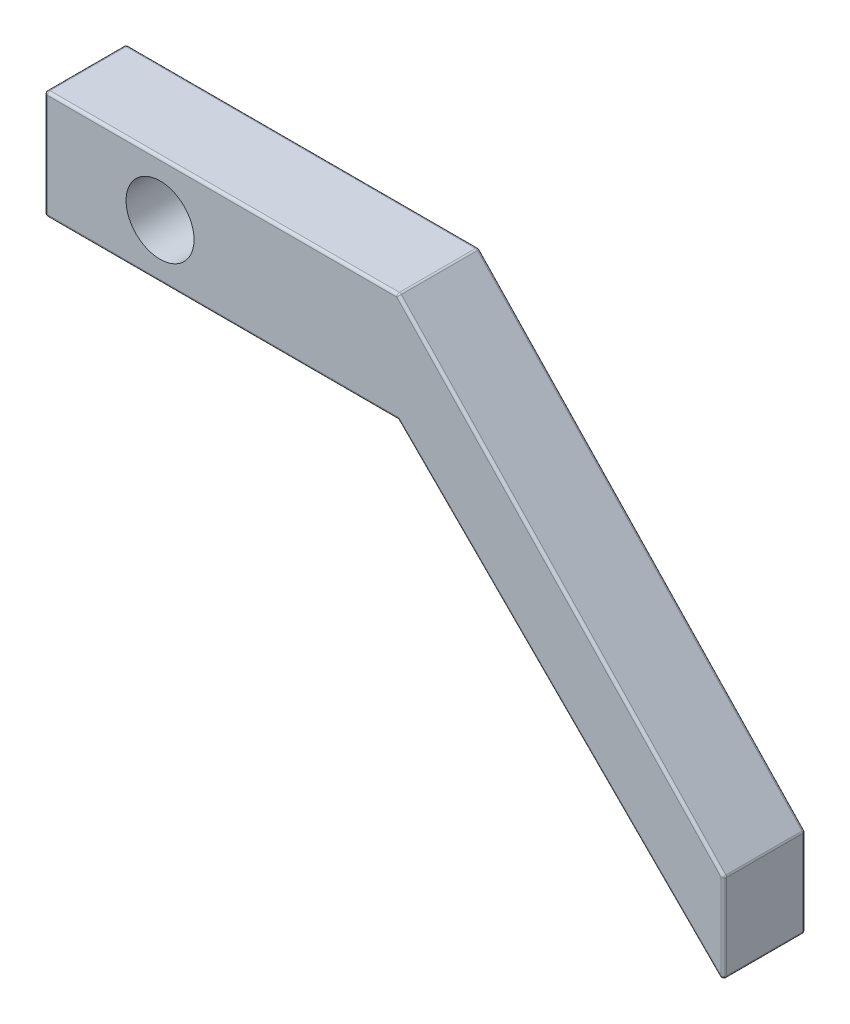
SolidWorks part; units mm, degrees
ref_plane "前视基准面" through (0, 0, 0) normal (0, 0, 1) x (1, 0, 0)
ref_plane "上视基准面" through (0, 0, 0) normal (0, 1, 0) x (1, 0, 0)
ref_plane "右视基准面" through (0, 0, 0) normal (1, 0, 0) x (0, 0, -1)
sketch "草图1" plane through (0, 0, 0) normal (0, 0, 1) x (1, 0, 0)
  line L0 (80, -20) -> (179.4574, -119.4574)
  line L1 (-80, 20) -> (80, 20)
  line L2 (-80, 20) -> (-80, -20)
  line L3 (-80, -20) -> (80, -20)
  line L4 (80, 20) -> (80, -20)
  line L5 (-80, 20) -> (80, -20) construction
  line L6 (-80, -20) -> (80, 20) construction
  line L7 (40, 20) -> (80, 20)
  line L8 (40, 20) -> (40, -20)
  line L9 (40, -20) -> (80, -20)
  line L10 (80, 20) -> (80, -20)
  line L11 (40, 20) -> (80, -20) construction
  line L12 (40, -20) -> (80, 20) construction
  line L13 (80, 20) -> (200, -105.8673)
  line L14 (200, -105.8673) -> (200, -140)
  line L15 (179.4574, -119.4574) -> (200, -140)
  point P0 (0, 0)
  point P6 (60, 0)
  dimension "D1" = 40
  dimension "D2" = 160
  dimension "D3" = 40
  dimension "D4" = 40
  dimension "D5" = 20
  dimension "D6" = 120
extrude "凸台-拉伸1" add sketch "草图1" along normal blind 40 contours L8 L1 L2 L3 | L1 L8 L3 L4 | L0 L15 L14 L13 L4 region at (138.4171, -59.8452, 0) region at (60, 0, 0) region at (-20, 0, 0)
sketch "草图2" plane through (0, 0, 40) normal (0, 0, 1) x (1, 0, 0)
  line L0 (-80, 20) -> (-80, -20) construction
  circle A0 centre (-60, 0) radius 12.5
  dimension "D1" = 20
extrude "切除-拉伸1" cut sketch "草图2" against normal blind 40
sketch "草图3" plane through (0, 0, 40) normal (0, 0, 1) x (1, 0, 0)
  line L1 (-239.6183, 159.8551) -> (239.6183, 159.8551)
  line L2 (-239.6183, 159.8551) -> (-239.6183, -159.8551)
  line L3 (-239.6183, -159.8551) -> (239.6183, -159.8551)
  line L4 (239.6183, 159.8551) -> (239.6183, -159.8551)
  line L5 (-239.6183, 159.8551) -> (239.6183, -159.8551) construction
  line L6 (-239.6183, -159.8551) -> (239.6183, 159.8551) construction
  point P0 (0, 0)
extrude "切除-拉伸2" cut sketch "草图3" against normal blind 10
pattern_linear "阵列(线性)2" count 2 spacing 52.5 along (1, 0, 0) of "切除-拉伸1"
sketch "草图5" plane through (0, 0, 30) normal (0, 0, 1) x (1, 0, 0)
  circle A0 centre (-60, 0) radius 17.3393
extrude "凸台-拉伸2" add sketch "草图5" against normal blind 30
sketch "草图6" plane through (0, 0, 30) normal (0, 0, 1) x (1, 0, 0)
  line L0 (-80, 20) -> (-80, -20) construction
  line L1 (-80, 20) -> (-50, 20)
  line L2 (-80, 20) -> (-80, -20)
  line L3 (-80, -20) -> (-50, -20)
  line L4 (-50, 20) -> (-50, -20)
  line L5 (-80, 20) -> (-50, -20) construction
  line L6 (-80, -20) -> (-50, 20) construction
  point P0 (-65, 0)
  dimension "D1" = 0
  dimension "D2" = 40
  dimension "D3" = 30
extrude "切除-拉伸3" cut sketch "草图6" against normal blind 30
fillet "圆角1" radius 1 7 edges at (140, -80, 30) (140, -80, 0) (140, -42.9336, 30) (200, -122.9336, 30) (200, -105.8673, 15) (200, -122.9336, 0) (140, -42.9336, 0)
fillet "圆角2" radius 1 14 edges at (79.5953, 20, 29.7071) (79.5953, 20, 0.2929) (199.7071, -139.2929, 29.7071) (199.7071, -139.2929, 0.2929) (-50, -20, 15) (-50, 0, 0) (-50, 0, 30) (-50, 20, 15) (80, 20, 15) (14.3092, 20, 30) (14.3092, 20, 0) (15.7071, -20, 30) (15.7071, -20, 0) (200, -140, 15)
